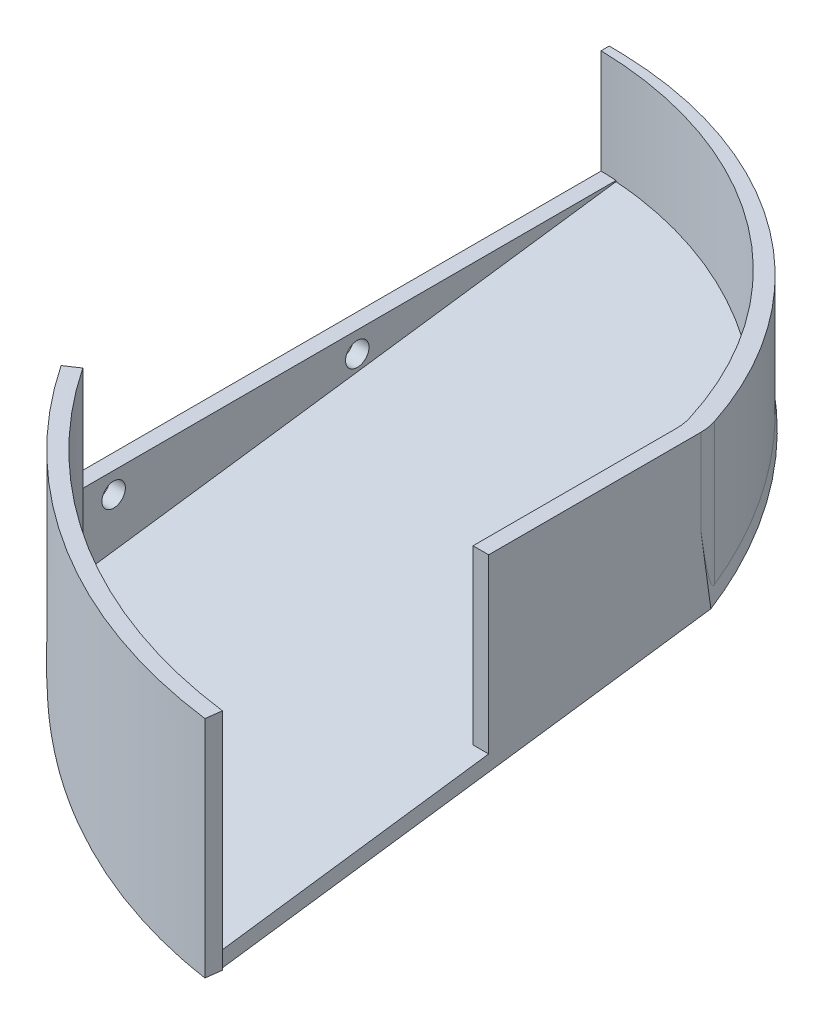
SolidWorks part; units mm, degrees
ref_plane "Front Plane" through (0, 0, 0) normal (0, 0, 1) x (1, 0, 0)
ref_plane "Top Plane" through (0, 0, 0) normal (0, 1, 0) x (1, 0, 0)
ref_plane "Right Plane" through (0, 0, 0) normal (1, 0, 0) x (0, 0, -1)
sketch "Sketch1" plane through (0, 0, 0) normal (1, 0, 0) x (0, 0, -1)
  line L0 (0, 0) -> (-150.2, -20.5184)
  line L1 (0, 0) -> (0, 3)
  line L2 (0, 3) -> (-150.2, 3)
  line L3 (-150.2, 3) -> (-150.2, -20.5184)
  dimension "D1" = 3
  dimension "D2" = 150.2
extrude "Boss-Extrude1" add sketch "Sketch1" along normal blind 3
sketch "Sketch2" plane through (0, 0, 0) normal (0, -0.9908, -0.1354) x (1, 0, 0)
  line L0 (3, 151.595) -> (0, 151.595) construction
  line L1 (3, 0) -> (73, 0)
  line L2 (3, 0) -> (3, 151.595)
  line L3 (3, 151.595) -> (73, 151.595)
  line L4 (73, 0) -> (73, 151.595)
  dimension "D1" = 70
extrude "Boss-Extrude2" add sketch "Sketch2" against normal blind 3
sketch "Sketch5" plane through (0, 3, 0) normal (0, 1, 0) x (1, 0, 0)
  line L0 (3, -104.0522) -> (0.5083, -105.723)
  line L1 (73, -150.6061) -> (73.3849, -147.6308)
  line L6 (70, -96.1466) -> (73, -96.1466)
  line L8 (3, 0) -> (3, -150.2) construction
  line L9 (3, -0.0595) -> (0, 0)
  line L10 (70, -96.1466) -> (70, -55.6681)
  line L11 (0, 0) -> (0, -1.5721)
  line L12 (73, -53.9086) -> (73, -96.1466)
  line L15 (73, -0.4061) -> (73, -150.6061) construction
  arc A0 (0.5083, -105.723) -> (73, -150.6061) centre (86.2426, -48.2346) ccw
  arc A1 (3, -104.0522) -> (73.3849, -147.6308) centre (86.2426, -48.2346) ccw
  arc A2 (0, -1.5721) -> (70, -55.6681) centre (-1.6608, -76.059) cw
  arc A3 (3, -0.0595) -> (73, -53.9086) centre (0.5055, -75.7242) cw
  dimension "D3" = 42.238
  dimension "D2" = 3
  dimension "D1" = 3
extrude "Boss-Extrude3" add sketch "Sketch5" along normal blind 20 and the other way blind 30
sketch "Sketch6" plane through (0, 3, 0) normal (0, 1, 0) x (1, 0, 0)
  line L0 (0.5083, -105.723) -> (0, -105.723)
  line L1 (0, -1.5721) -> (0, -150.2) construction
  line L2 (0, -105.723) -> (0, -169.0514)
  line L4 (0, -169.0514) -> (84.9815, -167.5759)
  line L5 (84.9815, -167.5759) -> (85.3151, -151.4548)
  arc A0 (0.5083, -105.723) -> (73, -150.6061) centre (86.2426, -48.2346) ccw construction
  arc A1 (0.5083, -105.723) -> (85.3151, -151.4548) centre (86.2426, -48.2346) ccw
extrude "Cut-Extrude2" cut sketch "Sketch6" against normal blind 33
sketch "Sketch8" plane through (0, 2.9724, 0.4061) normal (0, 0.9908, 0.1354) x (1, 0, 0)
  line L0 (8.1574, 0) -> (3.866, 8.2167)
  line L1 (3.866, 8.2167) -> (75.7058, 9.4387)
  line L2 (75.7058, 9.4387) -> (81.7063, -54.8115)
  line L3 (81.7063, -54.8115) -> (73, -53.9995)
  ellipse E0 centre (0.5055, -76.0176) end of major axis (0.5055, -152.4266) minor radius 75.7058 (73, -53.9995) -> (8.1574, 0) ccw construction
  ellipse E1 centre (0.5055, -76.0176) end of major axis (0.5055, -152.4266) minor radius 75.7058 (73, -53.9995) -> (8.1574, 0) ccw
extrude "Cut-Extrude4" cut sketch "Sketch8" against normal blind 115
fillet "Fillet1" radius 10 1 edges at (70, 9.2116, 55.6681)
fillet "Fillet2" radius 10 1 edges at (73, 9.3318, 53.9086)
sketch "Sketch9" plane through (0, 0, 0) normal (0, -0.9908, -0.1354) x (1, 0, 0)
  line L4 (3, 0) -> (8.1574, 0)
  line L5 (3, 0) -> (8.1574, 0)
  line L6 (73, 53.9995) -> (73, 54.4093)
  line L7 (73, 53.9995) -> (73, 54.4093)
  line L8 (3, 0.06) -> (0, 0)
  line L10 (3, 0.06) -> (0, 0)
  line L11 (0, 0) -> (3, 0)
  line L12 (0, 0) -> (3, 0)
  ellipse E0 centre (61.7447, 142.3321) end of major axis (63.9947, 142.3321) minor radius 2.2293 construction
  ellipse E1 centre (61.7447, 142.3321) end of major axis (63.9947, 142.3321) minor radius 2.2293
  ellipse E3 centre (0.5055, 76.0176) end of major axis (0.5055, 152.4266) minor radius 75.7058 (8.1574, 0) -> (73, 53.9995) ccw
  ellipse E4 centre (0.5055, 76.0176) end of major axis (0.5055, 152.4266) minor radius 75.7058 (8.1574, 0) -> (73, 53.9995) ccw
  ellipse E5 centre (0.5055, 76.4275) end of major axis (0.5055, 0.0185) minor radius 75.7058 (3, 0.06) -> (73, 54.4093) ccw
  ellipse E7 centre (0.5055, 76.4275) end of major axis (0.5055, 0.0185) minor radius 75.7058 (3, 0.06) -> (73, 54.4093) ccw
  dimension "D1" = 0
extrude "Cut-Extrude6" cut sketch "Sketch9" against normal up to next contours E1
sketch "Sketch10" plane through (3, 0, 0) normal (1, 0, 0) x (0, 0, -1)
  line L0 (-1.6995, 3) -> (-104.0522, 3) construction
  circle A0 centre (-98.132, -1) radius 2.25
  circle A1 centre (-51.3666, -1) radius 2.25
  dimension "D1" = 4.5
  dimension "D2" = 4.5
  dimension "D3" = 4
extrude "Cut-Extrude7" cut sketch "Sketch10" against normal up to next
sketch "Sketch11" plane through (70, 0, 0) normal (-1, 0, 0) x (0, 0, 1)
  line L0 (1.5721, -0.2148) -> (55.6681, -7.6047) construction
  line L1 (55.6681, -7.6047) -> (96.1466, -13.1343) construction
  line L2 (1.5721, -0.2148) -> (55.6681, -7.6047)
  line L3 (55.6681, -7.6047) -> (96.1466, -13.1343)
  line L4 (96.1466, -13.1343) -> (96.1466, -41.8898)
  line L5 (96.1466, -41.8898) -> (-9.4828, -44.1872)
  line L6 (-9.4828, -44.1872) -> (-10.5115, 3.1101)
  line L7 (-10.5115, 3.1101) -> (1.5721, -0.2148)
extrude "Cut-Extrude8" cut sketch "Sketch11" against normal up to next and the other way blind 94
sketch "Sketch13" plane through (49.061, 0, 73.1664) normal (-0.5569, 0, -0.8306) x (-0.8306, 0, 0.5569)
  line L0 (21.5602, -20.1606) -> (25.0582, -40.8163)
  line L1 (25.0582, -40.8163) -> (81.1182, -31.3227)
  line L2 (81.1182, -31.3227) -> (73.6982, -14.2143)
  line L3 (73.6982, -14.2143) -> (55.4539, -14.3129)
  ellipse E0 centre (-44.7667, -6.5892) end of major axis (-144.9873, 1.1344) minor radius 11.3384 (21.5602, -20.1606) -> (55.4577, -14.2143) ccw construction
  ellipse E1 centre (-44.7667, -6.5892) end of major axis (-144.9873, 1.1344) minor radius 11.3384 (21.5602, -20.1606) -> (55.4577, -14.2143) ccw
  line M1 (58.4577, -14.4425) -> (55.4577, -14.2143)
  line M2 (55.4577, -14.2143) -> (55.4577, -27)
  line M3 (55.4577, -27) -> (58.4577, -27)
  line M4 (58.4577, -27) -> (58.4577, -14.4425)
extrude "Cut-Extrude10" cut sketch "Sketch13" against normal blind 103 contours E1 L0 L1 L2 L3 M1 M4 M3 M2 | L3 M1 M2 M3 M4 region at (7.619, -27.0448, 100.955) region at (1.7565, -20.6741, 104.886)
sketch "Sketch14" plane through (90.96, 0, 11.7664) normal (0.9917, 0, 0.1283) x (0.1283, 0, -0.9917)
  line L0 (-139.6292, -20.123) -> (-133.4751, -20.123)
  line L1 (-133.4751, -20.123) -> (-133.4751, -31.4571)
  line L2 (-133.4751, -31.4571) -> (-143.1751, -29.8406)
  line L3 (-143.1751, -29.8406) -> (-139.6292, -20.123)
  arc A0 (-139.9964, -20.1161) -> (-137.4389, -20.1606) centre (-124.2532, 811.8598) ccw construction
extrude "Cut-Extrude11" cut sketch "Sketch14" against normal blind 103
